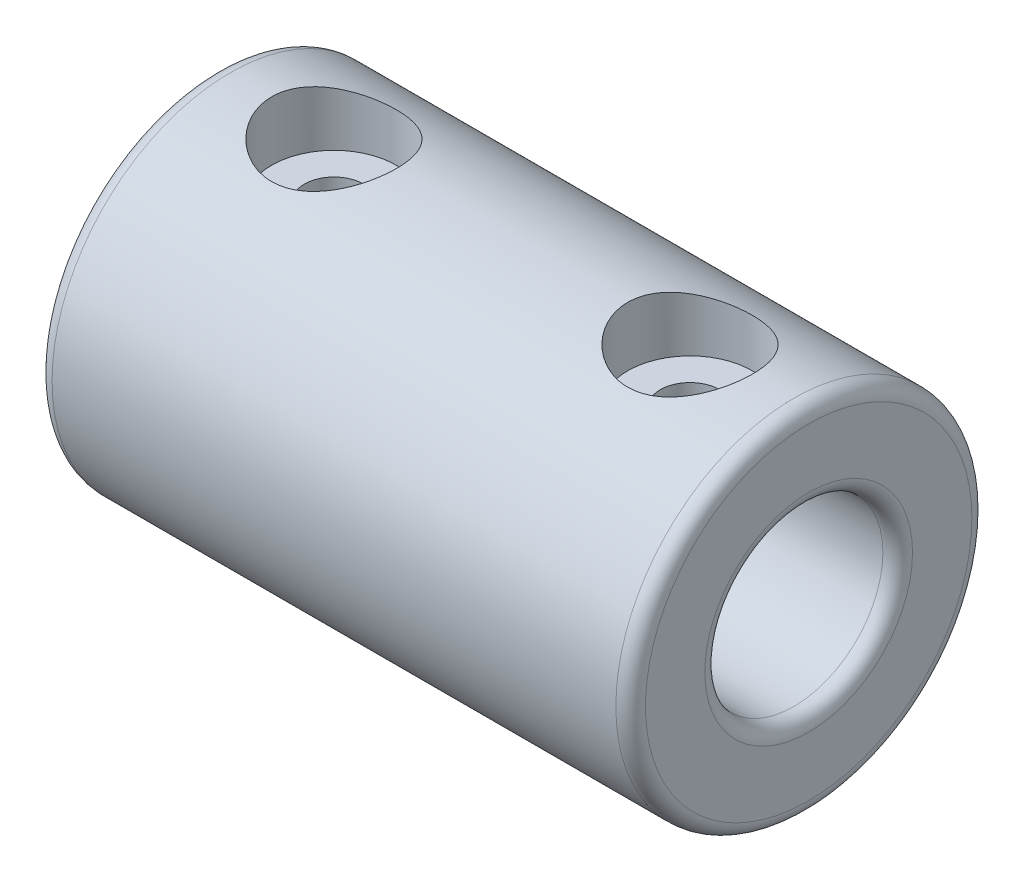
SolidWorks part; units mm, degrees
ref_plane "Front Plane" through (0, 0, 0) normal (0, 0, 1) x (1, 0, 0)
ref_plane "Top Plane" through (0, 0, 0) normal (0, 1, 0) x (1, 0, 0)
ref_plane "Right Plane" through (0, 0, 0) normal (1, 0, 0) x (0, 0, -1)
sketch "Sketch1" plane through (0, 0, 0) normal (1, 0, 0) x (0, 0, -1)
  circle A0 centre (0, 0) radius 6
  dimension "D1" = 12
extrude "Boss-Extrude1" add sketch "Sketch1" along normal blind 10 and the other way blind 10
sketch "Sketch2" plane through (10, 0, 0) normal (1, 0, 0) x (0, 0, -1)
  circle A0 centre (0, 0) radius 3
  dimension "D1" = 6
extrude "Cut-Extrude1" cut sketch "Sketch2" against normal blind 10
sketch "Sketch3" plane through (-10, 0, 0) normal (-1, 0, 0) x (0, 0, 1)
  circle A0 centre (0, 0) radius 2
  dimension "D1" = 4
extrude "Cut-Extrude2" cut sketch "Sketch3" against normal blind 10
sketch "Sketch4" plane through (0, 0, 0) normal (0, 1, 0) x (1, 0, 0)
  line L0 (-10, 0) -> (10, 0) construction
  line L1 (-10, 6) -> (-10, -6) construction
  line L2 (10, -6) -> (10, 6) construction
  circle A0 centre (-6, 0) radius 1
  circle A1 centre (6, 0) radius 1
  dimension "D3" = 2
  dimension "D4" = 2
  dimension "D1" = 4
  dimension "D2" = 4
extrude "Cut-Extrude4" cut sketch "Sketch4" along normal up to next
fillet "Fillet1" radius 0.5 4 edges at (10, 0, -3) (10, 0, -6) (-10, 0, -6) (-10, 0, 2)
ref_plane "Plane1" through (0, 6, 0) normal (0, 1, 0) x (1, 0, 0)
sketch "Sketch5" plane through (0, 6, 0) normal (0, 1, 0) x (1, 0, 0)
  circle A0 centre (-6, 0) radius 2.1
  circle A1 centre (6, 0) radius 2.1
  dimension "D1" = 4.2
  dimension "D2" = 4.2
extrude "Cut-Extrude7" cut sketch "Sketch5" against normal blind 2
